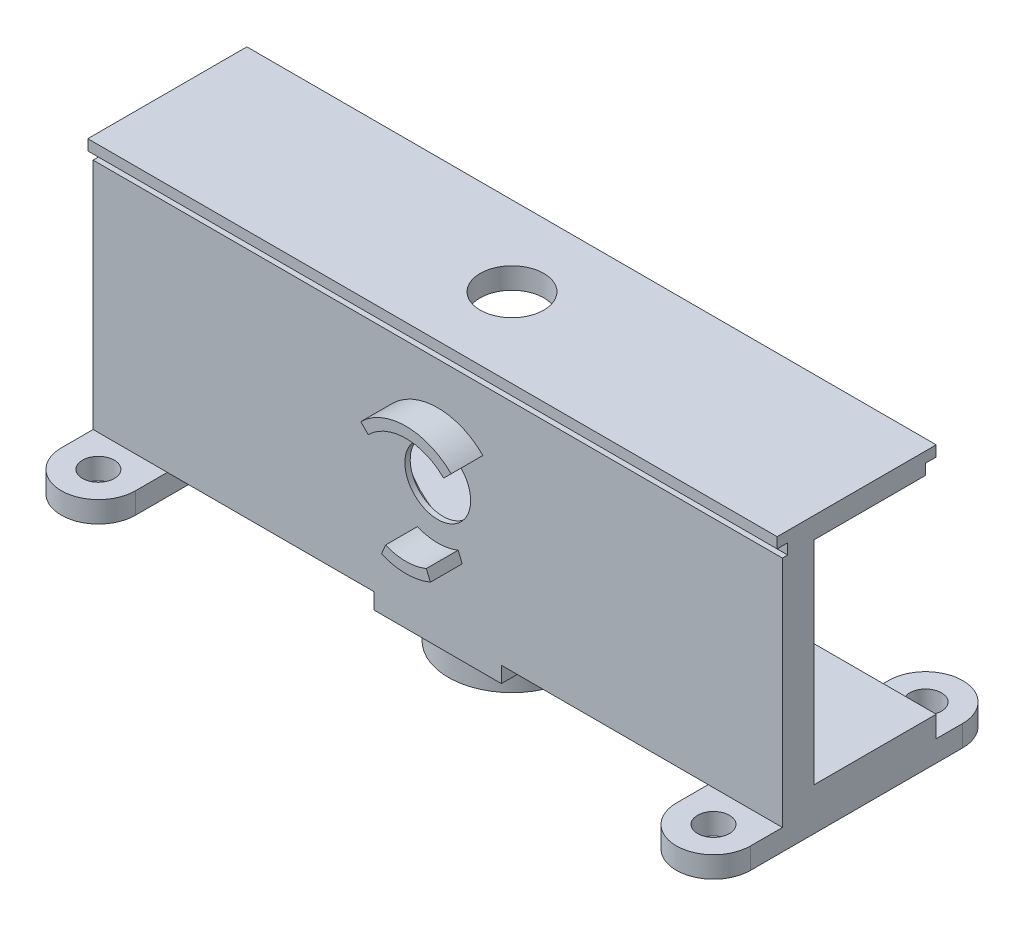
SolidWorks part; units mm, degrees
ref_plane "Alzado" through (0, 0, 0) normal (0, 0, 1) x (1, 0, 0)
ref_plane "Planta" through (0, 0, 0) normal (0, 1, 0) x (1, 0, 0)
ref_plane "Vista lateral" through (0, 0, 0) normal (1, 0, 0) x (0, 0, -1)
sketch "Croquis1" plane through (0, 0, 0) normal (1, 0, 0) x (0, 0, -1)
  line L1 (-7.5, 12) -> (7.5, 12)
  line L2 (-7.5, 12) -> (-7.5, -12)
  line L3 (-7.5, -12) -> (7.5, -12)
  line L4 (7.5, 12) -> (7.5, -12)
  line L5 (-7.5, 12) -> (7.5, -12) construction
  line L6 (-7.5, -12) -> (7.5, 12) construction
  point P0 (0, 0)
  dimension "D1" = 15
  dimension "D2" = 24
extrude "Saliente-Extruir1" add sketch "Croquis1" along normal blind 32.5 and the other way blind 32.5
sketch "Croquis2" plane through (32.5, 0, 0) normal (1, 0, 0) x (0, 0, -1)
  line L0 (7.5, 12) -> (-7.5, 12) construction
  line L1 (-7.5, 12) -> (-7.5, -12) construction
  line L2 (-7.5, 11) -> (-6.5, 11) construction
  line L3 (-6.5, 11) -> (-6.5, 10) construction
  line L4 (-6.5, 10) -> (-7, 10) construction
  line L5 (-7, 10) -> (-7, -12) construction
  line L6 (-7.5, -12) -> (7.5, -12) construction
  line L7 (-7, -12) -> (-7.5, -12) construction
  line L8 (-7.5, -12) -> (-7.5, 11) construction
  line L9 (-7.5, 11) -> (-6.5, 11)
  line L10 (-6.5, 11) -> (-6.5, 10)
  line L11 (-6.5, 10) -> (-7, 10)
  line L12 (-7, 10) -> (-7, -12)
  line L13 (-7, -12) -> (-7.5, -12)
  line L14 (-7.5, -12) -> (-7.5, 11)
  dimension "D1" = 1
  dimension "D2" = 1
  dimension "D3" = 1
  dimension "D4" = 0.5
extrude "Cortar-Extruir1" cut sketch "Croquis2" against normal blind 65.5
sketch "Croquis3" plane through (32.5, 0, 0) normal (1, 0, 0) x (0, 0, -1)
  line L0 (7.5, 11) -> (6.5, 11)
  line L1 (7.5, -12) -> (7.5, 12) construction
  line L2 (6.5, 11) -> (6.5, 10)
  line L3 (6.5, 10) -> (-4, 10)
  line L4 (-4, 10) -> (-4, -10)
  line L5 (-4, -10) -> (7.5, -10)
  line L6 (7.5, -10) -> (7.5, 11)
  line L8 (-7, -12) -> (7.5, -12) construction
  dimension "D1" = 1
  dimension "D2" = 10.5
  dimension "D3" = 2
extrude "Cortar-Extruir2" cut sketch "Croquis3" against normal blind 65.5
sketch "Croquis4" plane through (0, 0, 7) normal (0, 0, 1) x (1, 0, 0)
  line L2 (32.5, -12) -> (32.5, 10) construction
  line L5 (-3.5532, 3.5532) -> (-4.2603, 4.2603)
  line L7 (3.5532, 3.5532) -> (4.2603, 4.2603)
  line L9 (-1.923, -4.6425) -> (-2.3057, -5.5664)
  line L11 (1.923, -4.6425) -> (2.3057, -5.5664)
  arc A0 (-1.923, -4.6425) -> (1.923, -4.6425) centre (0, 0) ccw
  arc A1 (4.2603, 4.2603) -> (-4.2603, 4.2603) centre (0, 0) ccw
  arc A2 (-2.3057, -5.5664) -> (2.3057, -5.5664) centre (0, 0) ccw
  arc A3 (-3.5532, 3.5532) -> (3.5532, 3.5532) centre (0, 0) cw
  dimension "D1" = 5.025
  dimension "D2" = 6.025
  dimension "D3" = 30.1943
extrude "Saliente-Extruir2" add sketch "Croquis4" along normal blind 3
sketch "Croquis5" plane through (0, 0, 7) normal (0, 0, 1) x (1, 0, 0)
  circle A0 centre (0, 0) radius 3.1
  dimension "D1" = 6.2
extrude "Cortar-Extruir3" cut sketch "Croquis5" against normal blind 3
sketch "Croquis6" plane through (0, 0, 4) normal (0, 0, -1) x (-1, 0, 0)
  circle A0 centre (0, 0) radius 6.5
  dimension "D1" = 13
extrude "Cortar-Extruir5" cut sketch "Croquis6" against normal blind 2.5
sketch "Croquis7" plane through (0, -12, 0) normal (0, -1, 0) x (1, 0, 0)
  line L0 (-32.5, -7.5) -> (32.5, -7.5) construction
  line L1 (6, -7.5) -> (-6, -7.5)
  line L2 (6, -7.5) -> (6, 7)
  line L3 (6, 7) -> (-6, 7)
  line L4 (-6, -7.5) -> (-6, 7)
  line L5 (-32.5, 7) -> (32.5, 7) construction
  line L6 (-32.5, 7) -> (-32.5, -7.5) construction
  dimension "D1" = 26.5
  dimension "D2" = 38.5
extrude "Saliente-Extruir3" add sketch "Croquis7" along normal blind 1.5
sketch "Croquis8" plane through (0, -13.5, 0) normal (0, -1, 0) x (1, 0, 0)
  circle A0 centre (0, 0) radius 6
  circle A1 centre (0, 0) radius 3.5
  dimension "D1" = 12
  dimension "D2" = 2.5
extrude "Saliente-Extruir4" add sketch "Croquis8" along normal blind 3
sketch "Croquis9" plane through (0, -10, 0) normal (0, 1, 0) x (1, 0, 0)
  line L0 (-32.5, 7.5) -> (32.5, 7.5) construction
  line L1 (3, 7.5) -> (-3, 7.5)
  line L2 (3, 7.5) -> (3, 0.5)
  line L3 (-3, 0.5) -> (3, 0.5) construction
  line L4 (-3, 7.5) -> (-3, 0.5)
  arc A0 (3, 0.5) -> (-3, 0.5) centre (0, 0.5) cw
  dimension "D1" = 6
  dimension "D2" = 7
extrude "Cortar-Extruir6" cut sketch "Croquis9" against normal blind 2
sketch "Croquis10" plane through (0, -13.5, 0) normal (0, -1, 0) x (1, 0, 0)
  circle A0 centre (0, 0) radius 1.5
  dimension "D1" = 3
extrude "Cortar-Extruir7" cut sketch "Croquis10" against normal blind 2
sketch "Croquis11" plane through (0, 12, 0) normal (0, 1, 0) x (1, 0, 0)
  circle A0 centre (0, 0) radius 3
  dimension "D1" = 6
extrude "Cortar-Extruir8" cut sketch "Croquis11" against normal blind 2
sketch "Croquis12" plane through (0, -12, 0) normal (0, -1, 0) x (1, 0, 0)
  line L0 (32.5, -10) -> (32.5, 10)
  line L1 (25.5, -10) -> (25.5, 10)
  line L2 (-25.5, -10) -> (-25.5, 10)
  line L4 (-32.5, -10) -> (-32.5, 10)
  arc A0 (-25.5, 10) -> (-32.5, 10) centre (-29, 10) ccw
  arc A1 (-25.5, -10) -> (-32.5, -10) centre (-29, -10) cw
  circle A2 centre (-29, 10) radius 1.5
  circle A3 centre (-29, -10) radius 1.5
  arc A4 (32.5, 10) -> (25.5, 10) centre (29, 10) ccw
  arc A5 (32.5, -10) -> (25.5, -10) centre (29, -10) cw
  circle A6 centre (29, 10) radius 1.5
  circle A7 centre (29, -10) radius 1.5
  dimension "D2" = 3
  dimension "D4" = 3
  dimension "D7" = 3
  dimension "D8" = 3
  dimension "D1" = 20
  dimension "D3" = 7
  dimension "D5" = 20
  dimension "D6" = 7
  dimension "D9" = 10
  dimension "D10" = 10
  dimension "D11" = 25.5
  dimension "D12" = 51
extrude "Saliente-Extruir5" add sketch "Croquis12" along normal blind 2
